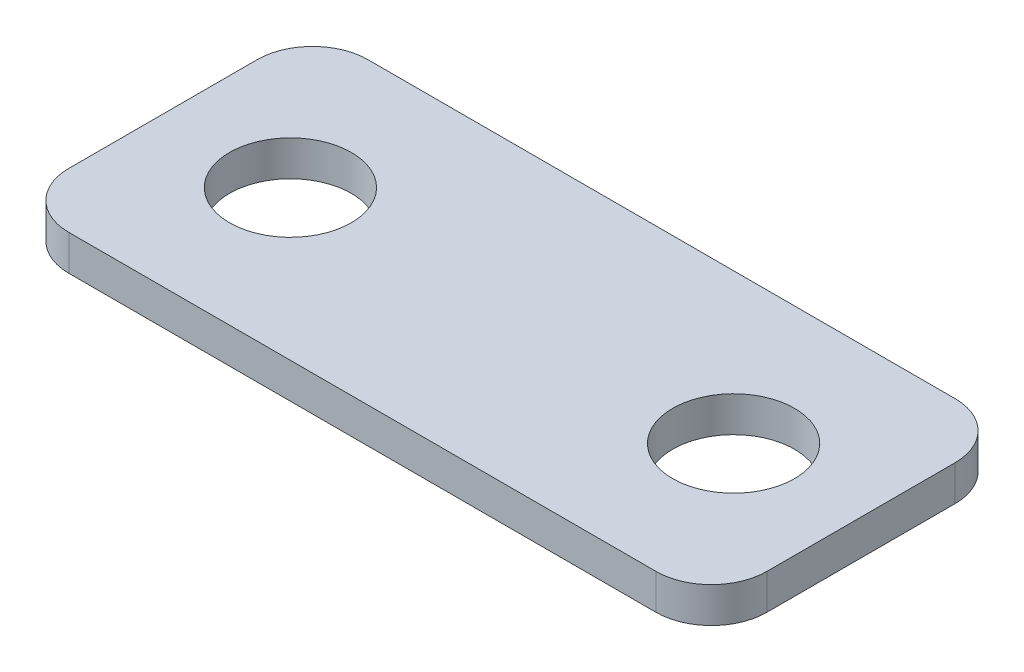
SolidWorks part; units mm, degrees
ref_plane "Front Plane" through (0, 0, 0) normal (0, 0, 1) x (1, 0, 0)
ref_plane "Top Plane" through (0, 0, 0) normal (0, 1, 0) x (1, 0, 0)
ref_plane "Right Plane" through (0, 0, 0) normal (1, 0, 0) x (0, 0, -1)
sketch "Sketch1" plane through (0, 0, 0) normal (0, 1, 0) x (1, 0, 0)
  line L0 (-20, 0) -> (20, 0) construction
  line L1 (26.5, -13.5) -> (-26.5, -13.5)
  line L2 (31.5, -8.5) -> (31.5, 8.5)
  line L3 (26.5, 13.5) -> (-26.5, 13.5)
  line L4 (-31.5, -8.5) -> (-31.5, 8.5)
  line L5 (31.5, -13.5) -> (-31.5, 13.5) construction
  line L6 (31.5, 13.5) -> (-31.5, -13.5) construction
  circle A0 centre (-20, 0) radius 5.5
  circle A1 centre (20, 0) radius 5.5
  arc A2 (26.5, -13.5) -> (31.5, -8.5) centre (26.5, -8.5) ccw
  arc A3 (31.5, 8.5) -> (26.5, 13.5) centre (26.5, 8.5) ccw
  arc A4 (-26.5, -13.5) -> (-31.5, -8.5) centre (-26.5, -8.5) cw
  arc A5 (-26.5, 13.5) -> (-31.5, 8.5) centre (-26.5, 8.5) ccw
  point P0 (0, 0)
  point P10 (0, 0)
  point P11 (0, 0)
  dimension "D3" = 11
  dimension "D5" = 6
  dimension "D7" = 5
  dimension "D1" = 27
  dimension "D2" = 63
  dimension "D4" = 40
  dimension "D6" = 8
base flange "Base-Flange1" sketch "Sketch1" thickness 3.2 reverse thickness direction no parameters "D1"=2.54
sketch "Bend-Lines1" [suppressed] plane through (0, 0, 0) normal (0, 1, 0) x (1, 0, 0)
sketch "Bounding-Box1" [suppressed] plane through (0, 0, 0) normal (0, 1, 0) x (1, 0, 0)
sheet metal parameters "Sheet-Metal1" thickness 3.2 parameters "D1"=2.54
flat pattern "Flat-Pattern1" [suppressed]
sketch "Bend-Lines2" plane through (0, 0, 0) normal (0, 1, 0) x (1, 0, 0)
sketch3d "Bounding-Box2" [suppressed]
  line L0 (-58, -5, 0) -> (5, -5, 0) construction
  line L1 (-58, 22, 0) -> (5, 22, 0) construction
  line L2 (-58, -5, 0) -> (-58, 22, 0) construction
  line L3 (5, -5, 0) -> (5, 22, 0) construction
